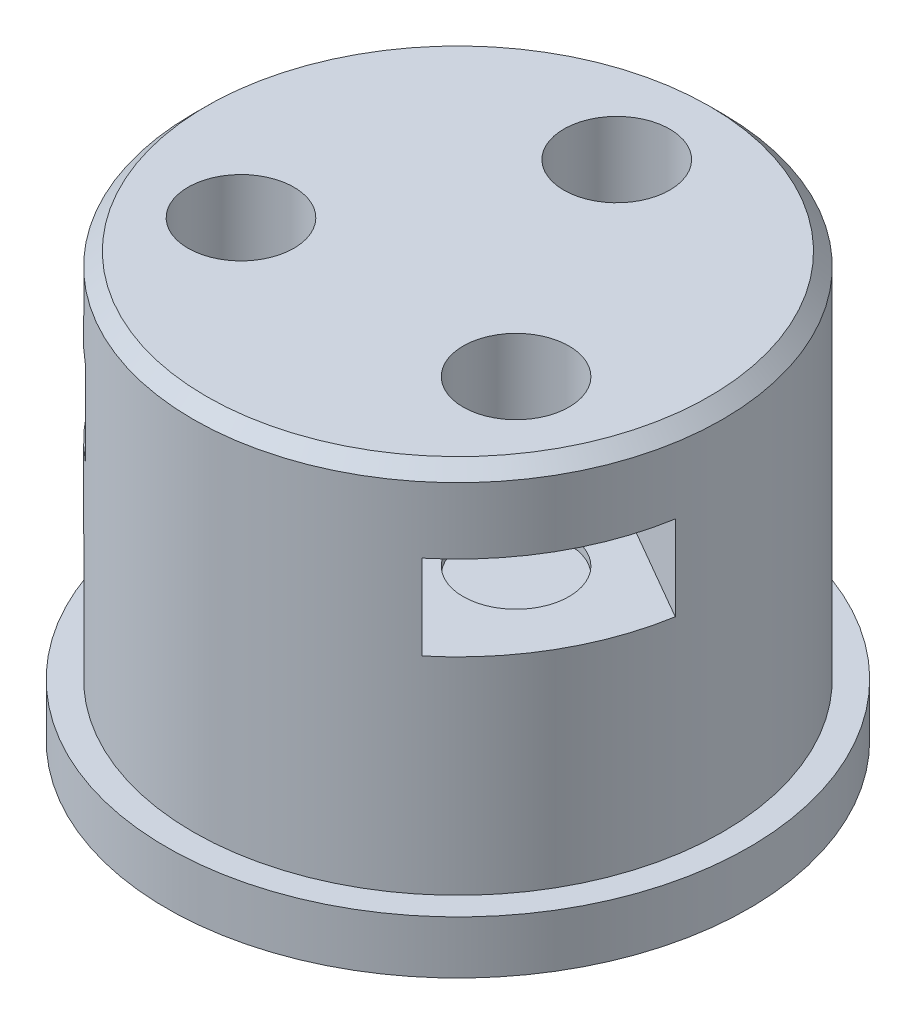
SolidWorks part; units mm, degrees
material "PLA"
ref_plane "Front Plane" through (0, 0, 0) normal (0, 0, 1) x (1, 0, 0)
ref_plane "Top Plane" through (0, 0, 0) normal (0, 1, 0) x (1, 0, 0)
ref_plane "Right Plane" through (0, 0, 0) normal (1, 0, 0) x (0, 0, -1)
sketch "Sketch1" plane through (0, 0, 0) normal (0, 1, 0) x (1, 0, 0)
  circle A0 centre (0, 0) radius 10
  circle A1 centre (0, 0) radius 8 construction
  dimension "D1" = 20
  dimension "D2" = 16
extrude "Boss-Extrude1" add sketch "Sketch1" along normal blind 16
sketch "Sketch2" plane through (0, 0, 0) normal (0, -1, 0) x (1, 0, 0)
  circle A0 centre (0, 0) radius 10 construction
  circle A1 centre (0, 0) radius 10
  circle A2 centre (0, 0) radius 11
extrude "Boss-Extrude2" add sketch "Sketch2" against normal blind 2
sketch "Sketch3" plane through (0, 0, 0) normal (0, -1, 0) x (1, 0, 0)
  circle A0 centre (0, 0) radius 8
  dimension "D1" = 16
extrude "Cut-Extrude1" cut sketch "Sketch3" against normal blind 6.5
sketch "Sketch4" plane through (0, 16, 0) normal (0, 1, 0) x (1, 0, 0)
  circle A0 centre (0, 0) radius 6 construction
  circle A1 centre (0, 6) radius 2
  circle A2 centre (5.1962, -3) radius 2
  circle A3 centre (-5.1962, -3) radius 2
  point P14 (0, 0)
  dimension "D1" = 12
  dimension "D2" = 4
  dimension "D3" = 3
extrude "Cut-Extrude2" cut sketch "Sketch4" against normal blind 6.5
sketch "Sketch5" plane through (0, 16, 0) normal (0, 1, 0) x (1, 0, 0)
  line L0 (-3.5, 8.0207) -> (-3.5, 9.3675)
  line L1 (0, 1.9585) -> (3.5, 3.9793)
  line L2 (3.5, 3.9793) -> (3.5, 8.0207)
  line L3 (3.5, 8.0207) -> (0, 10.0415)
  line L4 (0, 10.0415) -> (-3.5, 8.0207)
  line L5 (-3.5, 8.0207) -> (-3.5, 3.9793)
  line L6 (-3.5, 3.9793) -> (0, 1.9585)
  line L7 (3.5, 8.0207) -> (3.5, 9.3675)
  line L8 (8.6962, -0.9793) -> (9.8625, -1.6527)
  line L9 (8.6962, -0.9793) -> (5.1962, 1.0415)
  line L10 (8.6962, -5.0207) -> (8.6962, -0.9793)
  line L11 (5.1962, -7.0415) -> (8.6962, -5.0207)
  line L12 (5.1962, -7.0415) -> (6.3625, -7.7148)
  line L13 (1.6962, -5.0207) -> (5.1962, -7.0415)
  line L14 (1.6962, -0.9793) -> (1.6962, -5.0207)
  line L15 (5.1962, 1.0415) -> (1.6962, -0.9793)
  line L16 (-5.1962, -7.0415) -> (-6.3625, -7.7148)
  line L17 (-5.1962, -7.0415) -> (-1.6962, -5.0207)
  line L18 (-8.6962, -5.0207) -> (-5.1962, -7.0415)
  line L19 (-8.6962, -0.9793) -> (-8.6962, -5.0207)
  line L20 (-8.6962, -0.9793) -> (-9.8625, -1.6527)
  line L21 (-5.1962, 1.0415) -> (-8.6962, -0.9793)
  line L22 (-1.6962, -0.9793) -> (-5.1962, 1.0415)
  line L23 (-1.6962, -5.0207) -> (-1.6962, -0.9793)
  circle A0 centre (0, 6) radius 3.5 construction
  circle A1 centre (0, 0) radius 6 construction
  circle A3 centre (-5.1962, -3) radius 2
  circle A4 centre (-5.1962, -3) radius 2
  circle A5 centre (5.1962, -3) radius 2
  circle A6 centre (5.1962, -3) radius 2
  circle A7 centre (0, 6) radius 2
  circle A8 centre (0, 6) radius 2
  circle A9 centre (0, 0) radius 10 construction
  circle A10 centre (0, 0) radius 10
  point P50 (0, 0)
  circle M11 centre (0, 6) radius 2
  circle M12 centre (5.1962, -3) radius 2
  circle M13 centre (-5.1962, -3) radius 2
  circle M15 centre (0, 0) radius 10
  dimension "D5" = 7
  dimension "D4" = 0
  dimension "D6" = 3
extrude "Cut-Extrude3" cut sketch "Sketch5" against normal blind 3.2 from offset 3 contours L18 L16 M15 | L17 L23 L22 L21 L19 L18 M15 M13 | L19 L20 M15 | L5 L6 L1 L2 L3 L4 M15 M11 | L4 L0 M15 | L3 L7 M15 | L10 L8 M15 | L9 L15 L14 L13 L11 L10 M15 M12 | L11 L12 M15 region at (-2.2825, 16, -9.2115) region at (-1.7328, 16, -8.9179) region at (-9.1186, 16, 2.629) region at (2.2825, 16, -9.2115) region at (-6.8927, 16, 0.0615) region at (-6.8361, 16, 6.5825) region at (9.1186, 16, 2.629) region at (6.8361, 16, 6.5825) region at (8.5892, 16, 2.9583) offset against normal yes
sketch "Sketch6" plane through (0, 0, 0) normal (0, -1, 0) x (1, 0, 0)
  circle A0 centre (0, 0) radius 8
  circle A1 centre (0, 0) radius 7
  circle A2 centre (0, 0) radius 8 construction
extrude "Boss-Extrude3" add sketch "Sketch6" against normal up to surface (6.5 mm away) from offset 5 up to face at (0, 6.5, -8) offset against normal yes
chamfer "Chamfer1" distance 0.5 angle 45 1 edges at (0, 16, 10)
equation "\"Ns\" = 56"
equation "\"Np_b\" = 48"
equation "\"Np_s\" = 28"
equation "\"Nr_b\" = 152"
equation "\"module\" = 0.5"
equation "\"pressure_angle\" = 20.0"
equation "\"h_a\" = 0.5"
equation "\"h_f\" = 0.625"
equation "\"clr_tip_root\" = 0.125"
equation "\"dp_r_b\" = 76.0"
equation "\"db_r_b\" = 71.41663917972905"
equation "\"fw_r_b\" = 9.918018611286483"
equation "\"alpha_r_b\" = 0.8539582918412236"
equation "\"beta_r_b\" = 2.8921271099982366"
equation "\"bearing_ID\" = 60"
equation "\"bearing_OD\" = 78"
equation "\"bearing_height\" = 10"
equation "\"clearance_planet\" = 1.5"
equation "\"case_dist\" = 6.5"
equation "\"Motor_case_OD_max\" = 111.3"
equation "\"case_mounting_PCD\" = 103.8"
equation "\"bearing mount thickness\" = 8"
equation "\"case_mounting_hole_dia\" = 3"
equation "\"output_mounting_PCD\" = 86"
equation "\"output_mounting_hole_dia\" = 4"
equation "\"clearance_case_mount_holes_shell_thickness\" = 1"
equation "\"motor_case_OD_base\" = 101.8"
equation "\"sec_carrier_thickness\" = 5"
equation "\"sun_coupler_hub_thickness\" = 4"
equation "\"clearance_sun_coupler_sec_carrier\" = 1.5"
equation "\"clearance_motor_and_case\" = 5"
equation "\"motor_OD\" = 86.8"
equation "\"Motor_case_thickness\" = 2.5"
equation "\"Motor_case_ID\" = 96.8"
equation "\"case_mounting_hole_shift\" = 1.0"
equation "\"output_mounting_nut_wrench_size\" = 7"
equation "\"output_mounting_nut_thickness\" = 3.2"
equation "\"case_mounting_hole_allen_socket_dia\" = 5.5"
equation "\"output_mounting_nut_depth\" = 3"
equation "\"case_mounting_bolt_depth\" = 4.5"
equation "\"ring_radial_thickness\" = 5"
equation "\"ring_OD_b\" = 86.0"
equation "\"ring_to_chamfer_clearance\" = 1.5"
equation "\"Motor_case_OD_base_to_chamfer\" = 5"
equation "\"pattern_offset_from_motor_case_OD_base\" = 3"
equation "\"pattern_bulge_dia\" = 3"
equation "\"pattern_num_bulge\" = 18"
equation "\"pattern_depth\" = 2"
equation "\"motor_height\" = 26.5"
equation "\"case_mounting_wrench_size\" = 5.5"
equation "\"case_mounting_nut_clearance\" = 2"
equation "\"base_plate_thickness\" = 4"
equation "\"case_mounting_nut_thickness\" = 2.4"
equation "\"case_mounting_surface_height\" = 4"
equation "\"motor_mount_hole_PCD\" = 32"
equation "\"motor_mount_hole_dia\" = 4"
equation "\"motor_mount_hole_num\" = 4"
equation "\"central_hole_offset_from_motor_mount_PCD\" = 5"
equation "\"wire_slot_dist_from_center\" = 38"
equation "\"wire_slot_length\" = 10"
equation "\"wire_slot_radius\" = 2.5"
equation "\"driver_upper_holes_dist_from_center\" = 29"
equation "\"driver_lower_holes_dist_from_center\" = 13"
equation "\"driver_side_holes_dist_from_center\" = 22.5"
equation "\"driver_mount_holes_dia\" = 3"
equation "\"driver_mount_inserts_OD\" = 4.8"
equation "\"driver_mount_thickness\" = 1.5"
equation "\"driver_mount_height\" = 6"
equation "\"air_flow_hole_offset\" = 3"
equation "\"pressure angle\" = 20.0"
equation "\"h_b\" = 0.625"
equation "\"fw_p_s\" = 15.90536252346366"
equation "\"num_planet\" = 4"
equation "\"planet_pin_bolt_dia\" = 5"
equation "\"planet_pin_socket_head_dia\" = 8.5"
equation "\"carrier_PCD\" = 52.0"
equation "\"planet_shaft_dia\" = 8"
equation "\"planet_shaft_step_offset\" = 1"
equation "\"carrier_trapezoidal_support_sun_offset\" = 5"
equation "\"carrier_trapezoidal_support_hole_PCD_offset_bearing_ID\" = 4"
equation "\"carrier_trapezoidal_support_hole_dia\" = 3"
equation "\"carrier_trapezoidal_support_hole_socket_head_dia\" = 5.5"
equation "\"carrier_bearing_step_width\" = 1.5"
equation "\"standard_clearance_1_5mm\" = 1.5"
equation "\"standard_fillet_1_5mm\" = 1.5"
equation "\"sun_shaft_bearing_OD\" = 16"
equation "\"sun_shaft_bearing_width\" = 5"
equation "\"standard_bearing_insertion_chamfer\" = 0.5"
equation "\"carrier_trapezoidal_support_hole_wrench_size\" = 5.5"
equation "\"planet_pin_bolt_wrench_size\" = 8"
equation "\"planet_bearing_OD\" = 12"
equation "\"planet_bearing_width\" = 3.5"
equation "\"planet_bore\" = 10"
equation "\"motor_output_hole_PCD\" = 23"
equation "\"motor_output_hole_dia\" = 4"
equation "\"motor_output_hole_num\" = 4"
equation "\"dp_s\" = 28.0"
equation "\"db_s\" = 26.311393382005434"
equation "\"fw_s_calc\" = 2.7970255760332914"
equation "\"alpha_s\" = 0.8539582918412485"
equation "\"beta_s\" = 1.5063691306032174"
equation "\"dp_p_b\" = 24.0"
equation "\"db_p_b\" = 22.552622898861802"
equation "\"alpha_p_b\" = 0.8539582918412414"
equation "\"beta_p_b\" = 2.042083416317517"
equation "\"sun_shaft_bearing_ID\" = 8"
equation "\"sun_hub_dia\" = 30.0"
equation "\"sun_central_bolt_dia\" = 5"
equation "\"sun_central_bolt_socket_head_dia\" = 8.5"
equation "\"fw_s_used\" = 33.32338113475014"
equation "\"motor_output_hole_CSK_OD\" = 8"
equation "\"motor_output_hole_CSK_head_height\" = 2.0"
equation "\"bearing_retainer_thickness\" = 2"
equation "\"fw_p_b\" = 9.918018611286483"
equation "\"dp_p_s\" = 14.0"
equation "\"db_p_s\" = 13.155696691002717"
equation "\"alpha_p_s\" = 0.8539582918412485"
equation "\"beta_p_s\" = 4.720654844888932"
equation "\"Nr_s\" = 132"
equation "\"clr_tip_root_s\" = 0.125"
equation "\"dp_r_s\" = 66.0"
equation "\"db_r_s\" = 62.01971297186996"
equation "\"fw_r_s\" = 14.40536252346366"
equation "\"alpha_r_s\" = 0.8539582918412449"
equation "\"beta_r_s\" = 3.071552947318853"
equation "\"D1@Boss-Extrude1\"=\"bearing_height\" + \"carrier_thickness\" + \"carrier_small_ring_inner_bearing_flap\""
equation "\"D1@Cut-Extrude1\"=\"sun_shaft_bearing_width\" + \"standard_clearance_1_5mm\""
equation "\"D5@Sketch5\"=\"small_ring_output_wall_to_bearing_shaft_attachement_nut_wrench\""
equation "\"small_ring_case_thickness\" = 4"
equation "\"carrier_thickness\" = 4"
equation "\"small_ring_output_wall_thickness\" = 5"
equation "\"small_ring_output_wall_to_bearing_shaft_attachement_hole_dia\" = 4"
equation "\"small_ring_output_wall_to_bearing_shaft_attachement_hole_pcd\" = 12"
equation "\"small_ring_output_wall_to_bearing_shaft_attachement_hole_num\" = 3"
equation "\"small_ring_output_wall_to_bearing_shaft_attachement_hole_CSK_OD\" = 8"
equation "\"small_ring_output_wall_to_bearing_shaft_attachement_hole_CSK_head_height\" = 2.0"
equation "\"carrier_small_ring_inner_bearing_ID\" = 20"
equation "\"carrier_small_ring_inner_bearing_OD\" = 32"
equation "\"carrier_small_ring_inner_bearing_height\" = 7"
equation "\"D1@Sketch1\"=\"carrier_small_ring_inner_bearing_ID\""
equation "\"D2@Sketch1\"=\"sun_shaft_bearing_OD\""
equation "\"D1@Sketch2\"=\"standard_clearance_1_5mm\"*2/3"
equation "\"D1@Sketch3\"=\"sun_shaft_bearing_OD\""
equation "\"D1@Sketch4\"=\"small_ring_output_wall_to_bearing_shaft_attachement_hole_pcd\""
equation "\"D2@Sketch4\"=\"small_ring_output_wall_to_bearing_shaft_attachement_hole_dia\""
equation "\"D3@Sketch4\"=\"small_ring_output_wall_to_bearing_shaft_attachement_hole_num\""
equation "\"D6@Sketch5\"=\"small_ring_output_wall_to_bearing_shaft_attachement_hole_num\""
equation "\"D19@Cut-Extrude3\"=\"standard_clearance_1_5mm\"*2"
equation "\"D1@Sketch6\"=\"standard_clearance_1_5mm\"*2/3"
equation "\"D19@Boss-Extrude3\"=\"sun_shaft_bearing_width\""
equation "\"small_ring_output_wall_to_bearing_shaft_attachement_hole_depth\" = 6.5"
equation "\"small_ring_output_wall_to_bearing_shaft_attachement_nut_wrench\" = 7"
equation "\"small_ring_output_wall_to_bearing_shaft_attachement_nut_thickness\" = 3.2"
equation "\"carrier_small_ring_inner_bearing_flap\" = 2"
equation "\"D1@Boss-Extrude2\"=\"carrier_small_ring_inner_bearing_flap\""
equation "\"D1@Cut-Extrude2\"=\"small_ring_output_wall_to_bearing_shaft_attachement_hole_depth\""
equation "\"D1@Cut-Extrude3\"=\"small_ring_output_wall_to_bearing_shaft_attachement_nut_thickness\""
equation "\"D1@Chamfer1\"=\"standard_bearing_insertion_chamfer\""
